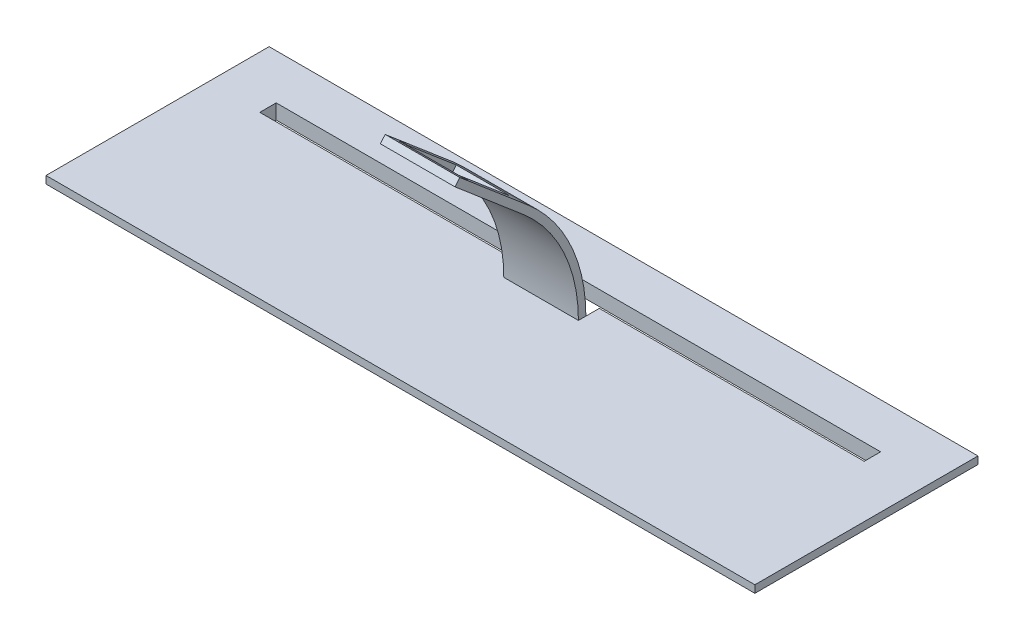
SolidWorks part; units mm, degrees
ref_plane "Front" through (0, 0, 0) normal (0, 0, 1) x (1, 0, 0)
ref_plane "Top" through (0, 0, 0) normal (0, 1, 0) x (1, 0, 0)
ref_plane "Right" through (0, 0, 0) normal (1, 0, 0) x (0, 0, -1)
sketch "Sketch1" plane through (0, 0, 0) normal (0, 1, 0) x (1, 0, 0)
  line L1 (-117.475, 34.798) -> (117.475, 34.798)
  line L2 (-117.475, 34.798) -> (-117.475, -34.798)
  line L3 (-117.475, -34.798) -> (117.475, -34.798)
  line L4 (117.475, 34.798) -> (117.475, -34.798)
  line L5 (-117.475, 34.798) -> (117.475, -34.798) construction
  line L6 (-117.475, -34.798) -> (117.475, 34.798) construction
  point P0 (0, 0)
  dimension "D1" = 69.596
  dimension "D2" = 234.95
extrude "Boss-Extrude1" add sketch "Sketch1" along normal blind 2.54
sketch "Sketch2" plane through (0, 2.54, 0) normal (0, 1, 0) x (1, 0, 0)
  line L8 (120.65, -37.973) -> (120.65, 37.973)
  line L9 (120.65, 37.973) -> (-120.65, 37.973)
  line L10 (-120.65, 37.973) -> (-120.65, -37.973)
  line L11 (-120.65, -37.973) -> (120.65, -37.973)
  line L12 (120.65, -37.973) -> (120.65, 37.973)
  line L13 (120.65, 37.973) -> (-120.65, 37.973)
  line L14 (-120.65, 37.973) -> (-120.65, -37.973)
  line L15 (-120.65, -37.973) -> (120.65, -37.973)
  dimension "D1" = 3.175
extrude "Boss-Extrude2" add sketch "Sketch2" along normal blind 2.54
sketch "Sketch3" plane through (0, 5.08, 0) normal (0, 1, 0) x (1, 0, 0)
  line L1 (-102.87, 22.606) -> (102.87, 22.606)
  line L2 (-102.87, 22.606) -> (-102.87, 12.446)
  line L3 (-102.87, 12.446) -> (102.87, 12.446)
  line L4 (102.87, 22.606) -> (102.87, 12.446)
  line L5 (120.65, 37.973) -> (-120.65, 37.973) construction
  line L6 (-12.7, 17.018) -> (-12.7, 12.446)
  line L7 (-102.87, 17.018) -> (102.87, 17.018)
  line L8 (-102.87, 17.018) -> (-102.87, 22.606)
  line L9 (-102.87, 22.606) -> (102.87, 22.606)
  line L10 (102.87, 17.018) -> (102.87, 22.606)
  line L13 (0, -31.2408) -> (0, 31.2408) construction
  line L14 (12.7, 17.018) -> (12.7, 12.446)
  point P0 (0, 0)
  point P8 (0, 0)
  dimension "D1" = 205.74
  dimension "D2" = 10.16
  dimension "D3" = 15.367
  dimension "D4" = 25.4
  dimension "D5" = 4.572
extrude "Cut-Extrude2" cut sketch "Sketch3" against normal through all contours L2 L7 L4 L1 | L14 L7 L6 L3 region at (0, 5.08, -19.812) region at (0, 5.08, -14.732)
sketch "Sketch4" plane through (0, 0, 0) normal (1, 0, 0) x (0, 0, -1)
  line L0 (22.606, 5.08) -> (17.018, 5.08) construction
  line L1 (22.606, 5.08) -> (17.018, 5.08)
  line L2 (-7.2411, 47.6552) -> (-8.8863, 45.72)
  line L4 (-37.973, 2.54) -> (37.973, 2.54)
  line L5 (37.973, 2.54) -> (37.973, 5.08)
  line L6 (37.973, 5.08) -> (-37.973, 5.08)
  line L7 (-37.973, 5.08) -> (-37.973, 2.54)
  line L8 (-37.973, 2.54) -> (37.973, 2.54)
  line L9 (37.973, 2.54) -> (37.973, 5.08)
  line L10 (37.973, 5.08) -> (-37.973, 5.08)
  line L11 (-37.973, 5.08) -> (-37.973, 2.54)
  line L14 (17.018, 5.08) -> (12.446, 5.08)
  line L15 (12.446, 5.08) -> (12.446, 0)
  line L16 (12.446, 0) -> (17.018, 0)
  line L17 (17.018, 0) -> (17.018, 5.08)
  line L18 (17.018, 5.08) -> (12.446, 5.08)
  line L19 (12.446, 5.08) -> (12.446, 0)
  line L20 (12.446, 0) -> (17.018, 0)
  line L21 (17.018, 0) -> (17.018, 5.08)
  arc A0 (12.446, 5.08) -> (-7.2411, 47.6552) centre (-43.434, 5.08) ccw
  arc A1 (9.906, 5.08) -> (-8.8863, 45.72) centre (-43.434, 5.08) ccw
  dimension "2" = 53.34
  dimension "D5" = 40.64
  dimension "D1" = 0
  dimension "D2" = 0
  dimension "D3" = 2.54
extrude "Boss-Extrude7" add sketch "Sketch4" along normal blind 12.7 and the other way blind 12.7 contours A1 L10 A0 L2 region at (0, 5.5562, -11.176)
sketch "Sketch5" plane through (0, 23.5648, 27.7203) normal (0, 0.6477, 0.7619) x (1, 0, 0)
  line L4 (-12.7, 29.0787) -> (12.7, 29.0787)
  line L5 (12.7, 29.0787) -> (12.7, 31.6187)
  line L6 (12.7, 31.6187) -> (-12.7, 31.6187)
  line L7 (-12.7, 31.6187) -> (-12.7, 29.0787)
  line L8 (-12.7, 29.0787) -> (12.7, 29.0787)
  line L9 (12.7, 29.0787) -> (12.7, 31.6187)
  line L10 (12.7, 31.6187) -> (-12.7, 31.6187)
  line L11 (-12.7, 31.6187) -> (-12.7, 29.0787)
  dimension "D1" = 0
extrude "Boss-Extrude8" add sketch "Sketch5" along normal blind 30.48
sketch "Sketch6" plane through (0, 24.0905, -20.4791) normal (0, 0.7619, -0.6477) x (1, 0, 0)
  line L0 (0, -31.2408) -> (0, 31.2408) construction
  line L1 (-9.144, -39.7558) -> (9.144, -39.7558)
  line L2 (-9.144, -39.7558) -> (-9.144, -62.7745)
  line L3 (-9.144, -62.7745) -> (9.144, -62.7745)
  line L4 (12.7, -36.3828) -> (-12.7, -36.3828)
  line L5 (-12.7, -36.3828) -> (-12.7, -66.8628)
  line L6 (-12.7, -66.8628) -> (12.7, -66.8628)
  line L7 (12.7, -66.8628) -> (12.7, -36.3828)
  line L8 (12.7, -36.3828) -> (-12.7, -36.3828)
  line L9 (-12.7, -36.3828) -> (-12.7, -66.8628)
  line L10 (-12.7, -66.8628) -> (12.7, -66.8628)
  line L11 (12.7, -66.8628) -> (12.7, -36.3828)
  line L12 (9.144, -39.7558) -> (9.144, -62.7745)
  line L13 (-9.144, -39.7558) -> (9.144, -62.7745) construction
  line L14 (-9.144, -62.7745) -> (9.144, -39.7558) construction
  point P2 (0, -51.2652)
  dimension "D2" = 18.288
  dimension "D3" = 23.0188
  dimension "D1" = 0
extrude "Cut-Extrude3" cut sketch "Sketch6" against normal up to next contours L12 L1 L2 L3 region at (0, 57.2944, 18.58)
sketch "Sketch9" plane through (0, 24.0905, -20.4791) normal (0, 0.7619, -0.6477) x (1, 0, 0)
  line L0 (0, -31.2408) -> (0, 31.2408) construction
  line L2 (-9.144, -39.7558) -> (9.144, -39.7558) construction
  circle A0 centre (-10.3187, -61.9808) radius 1
  circle A1 centre (10.3187, -61.9808) radius 1
  dimension "D3" = 2
  dimension "D1" = 22.225
  dimension "D2" = 20.6375
extrude "Cut-Extrude4" cut sketch "Sketch9" against normal up to next
